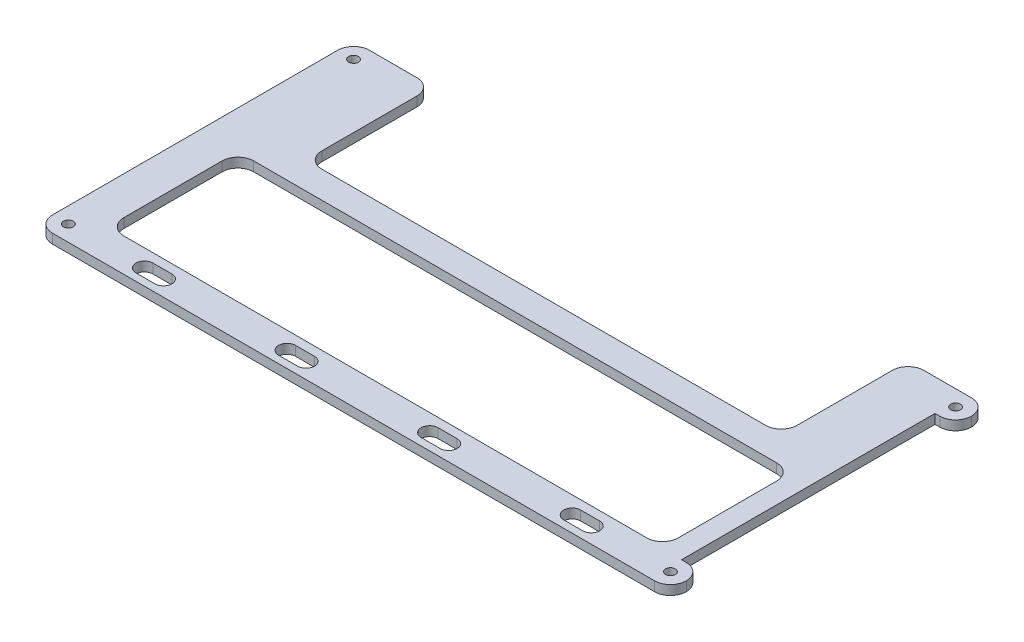
SolidWorks part; units mm, degrees
ref_plane "Front Plane" through (0, 0, 0) normal (0, 0, 1) x (1, 0, 0)
ref_plane "Top Plane" through (0, 0, 0) normal (0, 1, 0) x (1, 0, 0)
ref_plane "Right Plane" through (0, 0, 0) normal (1, 0, 0) x (0, 0, -1)
sketch "Sketch1" plane through (0, 0, 0) normal (0, 1, 0) x (1, 0, 0)
  line L1 (-100, 50) -> (100, 50)
  line L2 (-100, 50) -> (-100, -50)
  line L3 (-100, -50) -> (100, -50)
  line L4 (100, 50) -> (100, -50)
  line L5 (-100, 50) -> (100, -50) construction
  line L6 (-100, -50) -> (100, 50) construction
  point P0 (0, 0)
  dimension "D1" = 200
  dimension "D2" = 100
extrude "Boss-Extrude1" add sketch "Sketch1" along normal blind 3 contours L1 L4 L3 L2
sketch "Sketch2" plane through (0, 3, 0) normal (0, 1, 0) x (1, 0, 0)
  line L0 (-100, 50) -> (100, 50) construction
  line L1 (-100, 50) -> (-100, -50) construction
  line L2 (-100, -50) -> (100, -50) construction
  line L3 (100, 50) -> (100, -50) construction
  circle A0 centre (-95, 45) radius 1.55
  circle A1 centre (-95, -45) radius 1.55
  circle A2 centre (95, 45) radius 1.55
  circle A3 centre (95, -45) radius 1.55
  dimension "D3" = 3.1
  dimension "D4" = 3.1
  dimension "D5" = 3.1
  dimension "D6" = 3.1
  dimension "D1" = 5
  dimension "D2" = 5
  dimension "D7" = 5
  dimension "D8" = 5
  dimension "D9" = 5
  dimension "D10" = 5
  dimension "D11" = 5
  dimension "D12" = 5
extrude "Cut-Extrude1" cut sketch "Sketch2" against normal through all
fillet "Fillet1" radius 5 4 edges at (-100, 1.5, -50) (100, 1.5, -50) (100, 1.5, 50) (-100, 1.5, 50)
sketch "Sketch3" plane through (0, 3, 0) normal (0, 1, 0) x (1, 0, 0)
  line L0 (-95, 50) -> (95, 50) construction
  line L1 (-75, 50) -> (75, 50)
  line L2 (-75, 50) -> (-75, 10)
  line L3 (-75, 10) -> (75, 10)
  line L4 (75, 50) -> (75, 10)
  line L5 (-100, 45) -> (-100, -45) construction
  line L6 (100, 45) -> (100, -45) construction
  line L7 (-95, -50) -> (95, -50) construction
  line L8 (100, 40) -> (93.5, 40)
  line L9 (100, 40) -> (100, -40)
  line L10 (100, -40) -> (93.5, -40)
  line L11 (93.5, 40) -> (93.5, -40)
  line L16 (-100, -45) -> (100, -45) construction
  line L17 (-71, -45) -> (-65, -45) construction
  line L18 (-88, 1.5) -> (87, 1.5)
  line L19 (-88, 1.5) -> (-88, -39.5)
  line L20 (-88, -39.5) -> (87, -39.5)
  line L21 (87, 1.5) -> (87, -39.5)
  line L22 (-88, 1.5) -> (87, -39.5) construction
  line L23 (-88, -39.5) -> (87, 1.5) construction
  line L24 (-71, -42.318) -> (-65, -42.318)
  line L25 (-71, -47.682) -> (-65, -47.682)
  line L26 (-26, -45) -> (-20, -45) construction
  line L27 (-26, -42.318) -> (-20, -42.318)
  line L28 (-26, -47.682) -> (-20, -47.682)
  line L29 (19, -45) -> (25, -45) construction
  line L30 (19, -42.318) -> (25, -42.318)
  line L31 (19, -47.682) -> (25, -47.682)
  line L32 (64, -45) -> (70, -45) construction
  line L33 (64, -42.318) -> (70, -42.318)
  line L34 (64, -47.682) -> (70, -47.682)
  arc A0 (-71, -42.318) -> (-71, -47.682) centre (-71, -45) ccw
  arc A1 (-65, -47.682) -> (-65, -42.318) centre (-65, -45) ccw
  arc A2 (-26, -42.318) -> (-26, -47.682) centre (-26, -45) ccw
  arc A3 (-20, -47.682) -> (-20, -42.318) centre (-20, -45) ccw
  arc A4 (19, -42.318) -> (19, -47.682) centre (19, -45) ccw
  arc A5 (25, -47.682) -> (25, -42.318) centre (25, -45) ccw
  arc A6 (64, -42.318) -> (64, -47.682) centre (64, -45) ccw
  arc A7 (70, -47.682) -> (70, -42.318) centre (70, -45) ccw
  point P20 (-68, -45)
  point P22 (-0.5, -19)
  point P32 (-23, -45)
  point P38 (22, -45)
  point P45 (67, -45)
  dimension "D11" = 5
  dimension "D12" = 6
  dimension "D13" = 32
  dimension "D14" = 77
  dimension "D1" = 25
  dimension "D2" = 25
  dimension "D3" = 40
  dimension "D4" = 10
  dimension "D5" = 10
  dimension "D6" = 6.5
  dimension "D7" = 12
  dimension "D8" = 8.5
  dimension "D9" = 6.5
  dimension "D10" = 31
  dimension "D15" = 122
  dimension "D16" = 167
extrude "Cut-Extrude2" cut sketch "Sketch3" against normal through all
fillet "Fillet2" radius 5 10 edges at (75, 1.5, -10) (75, 1.5, -50) (100, 1.5, -40) (100, 1.5, 40) (-75, 1.5, -10) (-75, 1.5, -50) (87, 1.5, 39.5) (87, 1.5, -1.5) (-88, 1.5, 39.5) (-88, 1.5, -1.5)
